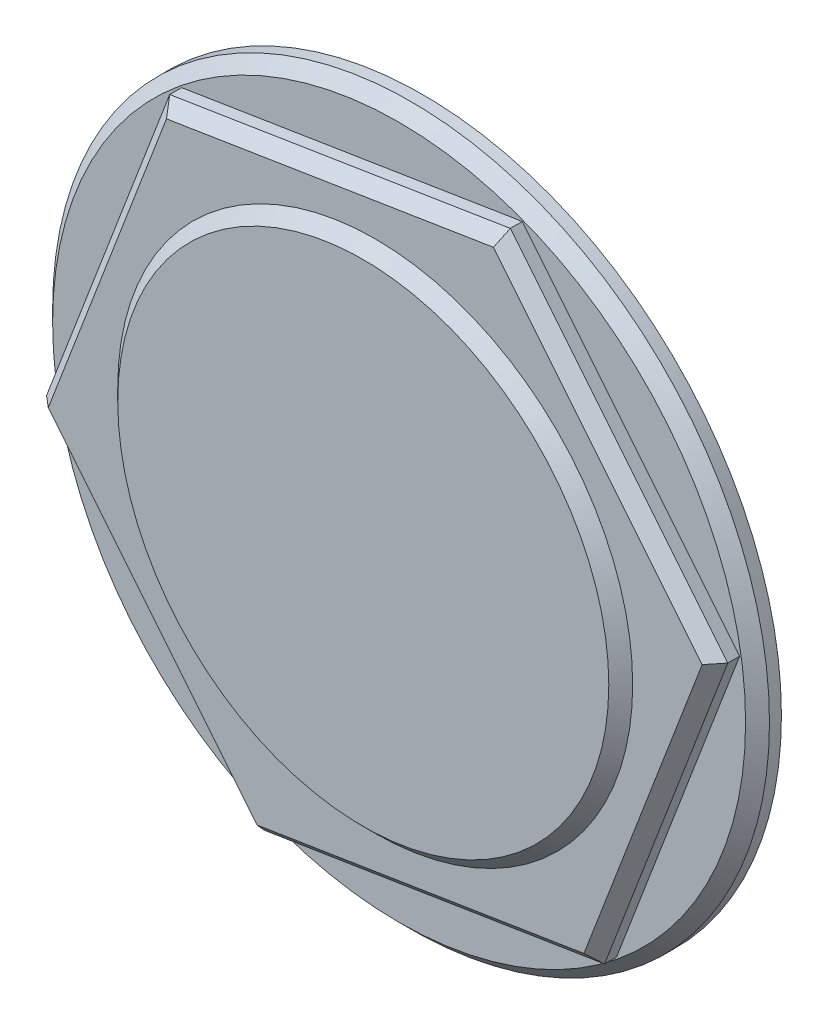
SolidWorks part; units mm, degrees
material "AISI 4340 Сталь, отожженная"
ref_plane "Спереди" through (0, 0, 0) normal (0, 0, 1) x (1, 0, 0)
ref_plane "Сверху" through (0, 0, 0) normal (0, 1, 0) x (1, 0, 0)
ref_plane "Справа" through (0, 0, 0) normal (1, 0, 0) x (0, 0, -1)
sketch "Эскиз1" plane through (0, 0, 0) normal (0, 0, 1) x (1, 0, 0)
  circle A0 centre (-49.3312, 19.9456) radius 30
extrude "Бобышка-Вытянуть1" add sketch "Эскиз1" along normal blind 2
sketch "Эскиз2" plane through (0, 0, 2) normal (0, 0, 1) x (1, 0, 0)
  line L1 (-20.8252, 24.4998) -> (-39.0222, 46.9096)
  line L2 (-39.0222, 46.9096) -> (-67.5282, 42.3555)
  line L3 (-67.5282, 42.3555) -> (-77.8372, 15.3915)
  line L4 (-77.8372, 15.3915) -> (-59.6402, -7.0184)
  line L5 (-59.6402, -7.0184) -> (-31.1341, -2.4642)
  line L6 (-31.1341, -2.4642) -> (-20.8252, 24.4998)
  circle A0 centre (-49.3312, 19.9456) radius 25 construction
extrude "Бобышка-Вытянуть2" add sketch "Эскиз2" along normal blind 2
sketch "Эскиз3" plane through (0, 0, 4) normal (0, 0, 1) x (1, 0, 0)
  circle A0 centre (-49.3312, 19.9456) radius 21.5498
extrude "Бобышка-Вытянуть3" add sketch "Эскиз3" along normal blind 1
chamfer "Фаска1" distance 1 angle 45 6 edges at (-25.9797, 11.0178, 4) (-45.3872, -4.7413, 4) (-68.7387, 4.1865, 4) (-72.6827, 28.8735, 4) (-53.2752, 44.6326, 4) (-29.9237, 35.7047, 4)
chamfer "Фаска2" distance 1 angle 45 1 edges at (-27.7814, 19.9456, 5)
chamfer "Фаска3" distance 1 angle 45 1 edges at (-19.3312, 19.9456, 2)
